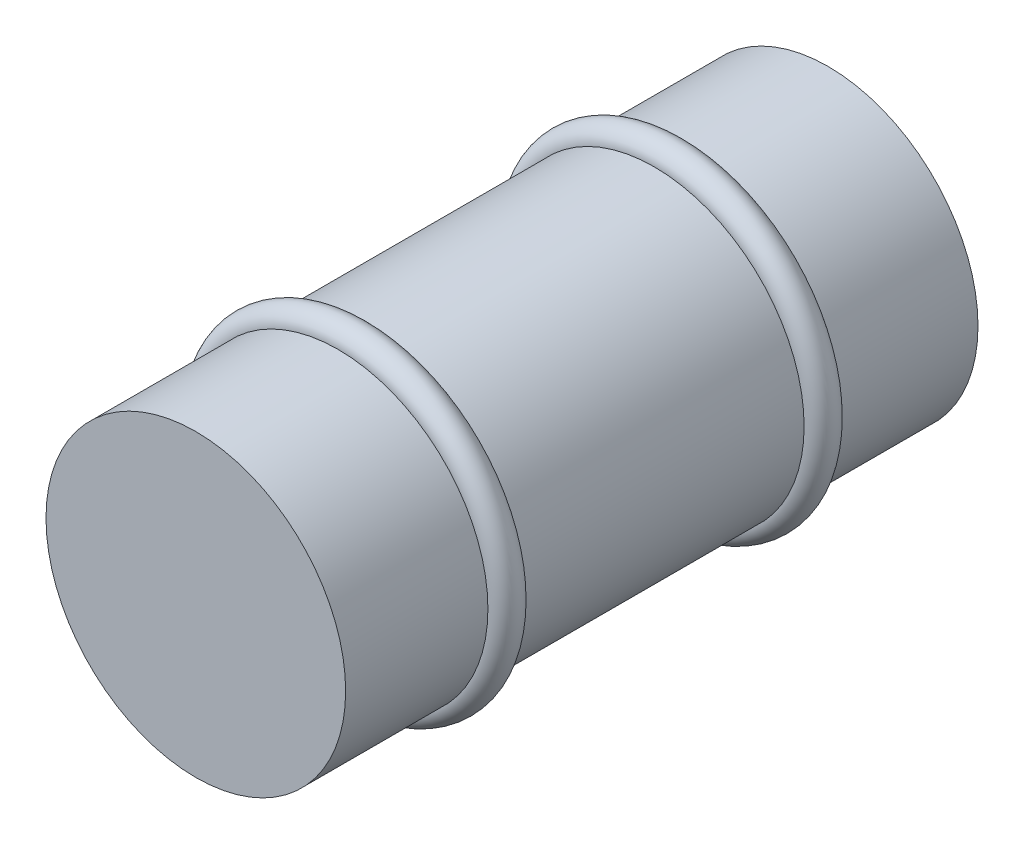
SolidWorks part; units mm, degrees
ref_plane "Front" through (0, 0, 0) normal (0, 0, 1) x (1, 0, 0)
ref_plane "Top" through (0, 0, 0) normal (0, 1, 0) x (1, 0, 0)
ref_plane "Right" through (0, 0, 0) normal (1, 0, 0) x (0, 0, -1)
sketch "Sketch1" plane through (0, 0, 0) normal (0, 0, 1) x (1, 0, 0)
  circle A0 centre (0, 0) radius 23.6929
extrude "Boss-Extrude1" add sketch "Sketch1" along normal blind 100
ref_plane "Plane2" through (0, 0, 100) normal (0, 0, 1) x (1, 0, 0)
ref_plane "Plane3" through (0, 0, 75) normal (0, 0, 1) x (1, 0, 0)
sketch "Sketch3" plane through (0, 0, 75) normal (0, 0, 1) x (1, 0, 0)
  line L0 (0, 0) -> (23.6077, 0) construction
  circle A0 centre (0, 0) radius 23.6929 construction
  circle A1 centre (0, 0) radius 23.6929
  point P3 (23.6077, 0)
  point P5 (0, 0)
ref_plane "Plane5" through (23.6077, 0, 75) normal (0, 1, 0) x (1, 0, 0)
sketch "Sketch4" plane through (23.6077, 0, 75) normal (0, 1, 0) x (1, 0, 0)
  line L0 (-47.3006, 0) -> (0.0853, 0) construction
  line L1 (0.0853, -25) -> (0.0853, 75) construction
  circle A0 centre (0.0853, 0) radius 2.5
  dimension "D1" = 5
sweep "Cut-Sweep1" cut profiles "Sketch4" path "Sketch3"
sketch "Sketch5" plane through (23.6077, 0, 75) normal (0, 1, 0) x (1, 0, 0)
  circle A0 centre (0.0853, 0) radius 2.5
  arc A1 (0.0853, 2.5) -> (0.0853, -2.5) centre (0.0853, 0) ccw construction
sweep "Sweep1" add profiles "Sketch5" path "Sketch3<2>"
sketch "Sketch3<2>" plane through (0, 0, 75) normal (0, 0, 1) x (1, 0, 0) same geometry as "Sketch3"
sketch "Sketch6" plane through (0, 0, 0) normal (0, 1, 0) x (1, 0, 0)
  line L0 (0, 0) -> (0, -46.4777) construction
pattern_linear "LPattern1" count 2 spacing 50 along (0, 0, -1) of bodies 103
